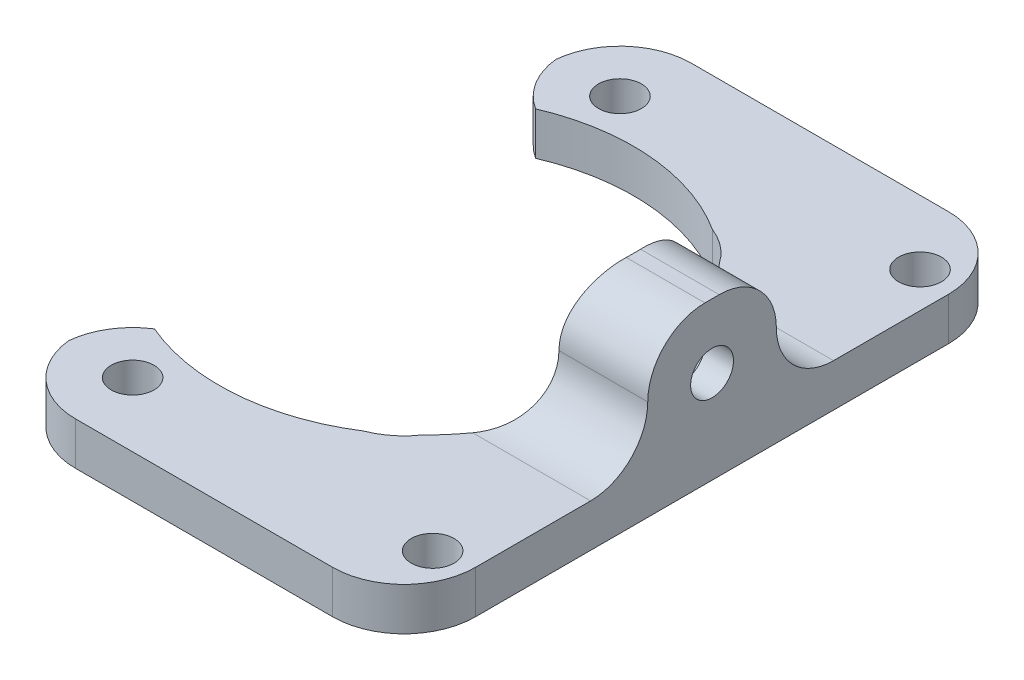
SolidWorks part; units mm, degrees
ref_plane "Plan de face" through (0, 0, 0) normal (0, 0, 1) x (1, 0, 0)
ref_plane "Plan de dessus" through (0, 0, 0) normal (0, 1, 0) x (1, 0, 0)
ref_plane "Plan de droite" through (0, 0, 0) normal (1, 0, 0) x (0, 0, -1)
sketch "Esquisse1" plane through (0, 0, 0) normal (0, 1, 0) x (1, 0, 0)
  line L0 (-36.6637, 22.2555) -> (-36.6637, 13.2555)
  line L1 (-36.6637, 13.2555) -> (-17.6637, 13.2555)
  line L2 (-17.6637, 13.2555) -> (-17.6637, -11.8545)
  line L3 (-17.6637, -11.8545) -> (-36.6637, -11.8545)
  line L4 (-36.6637, -11.8545) -> (-36.6637, -20.8545)
  line L5 (-36.6637, -20.8545) -> (-8.6637, -20.8545)
  line L6 (-8.6637, -20.8545) -> (-8.6637, 22.2555)
  line L7 (-8.6637, 22.2555) -> (-36.6637, 22.2555)
  circle A0 centre (-32.1637, 17.7555) radius 1.5
  circle A1 centre (-11.1637, 17.7555) radius 1.5
  circle A2 centre (-32.1637, -16.3545) radius 1.5
  circle A3 centre (-11.1637, -16.3545) radius 1.5
  dimension "D3" = 3
  dimension "D4" = 3
  dimension "D5" = 3
  dimension "D6" = 3
  dimension "D7" = 4.5
  dimension "D8" = 4.5
  dimension "D9" = 2.5
  dimension "D10" = 4.5
  dimension "D11" = 2.5
  dimension "D12" = 4.5
  dimension "D13" = 21
  dimension "D14" = 4.5
  dimension "D15" = 4.5
  dimension "D16" = 21
  dimension "D18" = 34.11
  dimension "D1" = 9
  dimension "D2" = 9
  dimension "D17" = 9
extrude "Boss.-Extru.1" add sketch "Esquisse1" along normal blind 3
sketch "Esquisse2" plane through (0, 3, 0) normal (0, 1, 0) x (1, 0, 0)
  line L0 (-17.6637, 13.2555) -> (-17.6637, -11.8545) construction
  line L1 (-17.6637, 5.2005) -> (-8.6637, 5.2005)
  line L2 (-17.6637, 5.2005) -> (-17.6637, -3.7995)
  line L3 (-17.6637, -3.7995) -> (-8.6637, -3.7995)
  line L4 (-8.6637, 5.2005) -> (-8.6637, -3.7995)
  line L5 (-17.6637, 5.2005) -> (-8.6637, -3.7995) construction
  line L6 (-17.6637, -3.7995) -> (-8.6637, 5.2005) construction
  line L7 (-8.6637, -20.8545) -> (-8.6637, 22.2555) construction
  point P4 (-13.1637, 0.7005)
  point P9 (-17.6637, 0.7005)
  dimension "D1" = 9
  dimension "D2" = 0
extrude "Boss.-Extru.2" add sketch "Esquisse2" along normal blind 8
sketch "Esquisse3" plane through (-17.6637, 0, 0) normal (-1, 0, 0) x (0, 0, 1)
  line L1 (3.7995, 3) -> (11.8545, 3) construction
  line L2 (-5.2005, 11) -> (-5.2005, 3) construction
  circle A0 centre (-0.7005, 6.5) radius 1.5
  dimension "D1" = 3
  dimension "D2" = 3.5
  dimension "D3" = 4.5
extrude "Enlèv. mat.-Extru.1" cut sketch "Esquisse3" against normal through all
sketch "Esquisse4" plane through (-17.6637, 0, 0) normal (-1, 0, 0) x (0, 0, 1)
  line L1 (0.7869, 3.5644) -> (2.5855, 6.3204)
  line L2 (2.5855, 6.3204) -> (1.098, 9.2559)
  line L3 (1.098, 9.2559) -> (-2.188, 9.4356)
  line L4 (-2.188, 9.4356) -> (-3.9865, 6.6796)
  line L5 (-3.9865, 6.6796) -> (-2.4991, 3.7441)
  line L6 (-2.4991, 3.7441) -> (0.7869, 3.5644)
  circle A0 centre (-0.7005, 6.5) radius 2.85 construction
  dimension "D1" = 5.7
extrude "Enlèv. mat.-Extru.2" cut sketch "Esquisse4" against normal blind 7
fillet "Congé1" radius 5 8 edges at (-8.6637, 1.5, 20.8545) (-36.6637, 1.5, 20.8545) (-36.6637, 1.5, 11.8545) (-17.6637, 1.5, 11.8545) (-17.6637, 1.5, -13.2555) (-36.6637, 1.5, -13.2555) (-8.6637, 1.5, -22.2555) (-36.6637, 1.5, -22.2555)
fillet "Congé2" radius 4 2 edges at (-13.1637, 11, -5.2005) (-13.1637, 11, 3.7995)
fillet "Congé3" radius 4 2 edges at (-13.1637, 3, 3.7995) (-13.1637, 3, -5.2005)
sketch "Esquisse5" plane through (0, 3, 0) normal (0, 1, 0) x (1, 0, 0)
  line L0 (-32.1637, 17.7555) -> (-32.1637, -16.3545) construction
  line L1 (-32.1637, 0.7005) -> (-28.6637, 0.7005) construction
  circle A0 centre (-28.6637, 0.7005) radius 14.5
  dimension "D2" = 29
  dimension "D1" = 3.5
extrude "Enlèv. mat.-Extru.3" cut sketch "Esquisse5" against normal through all and the other way through all
